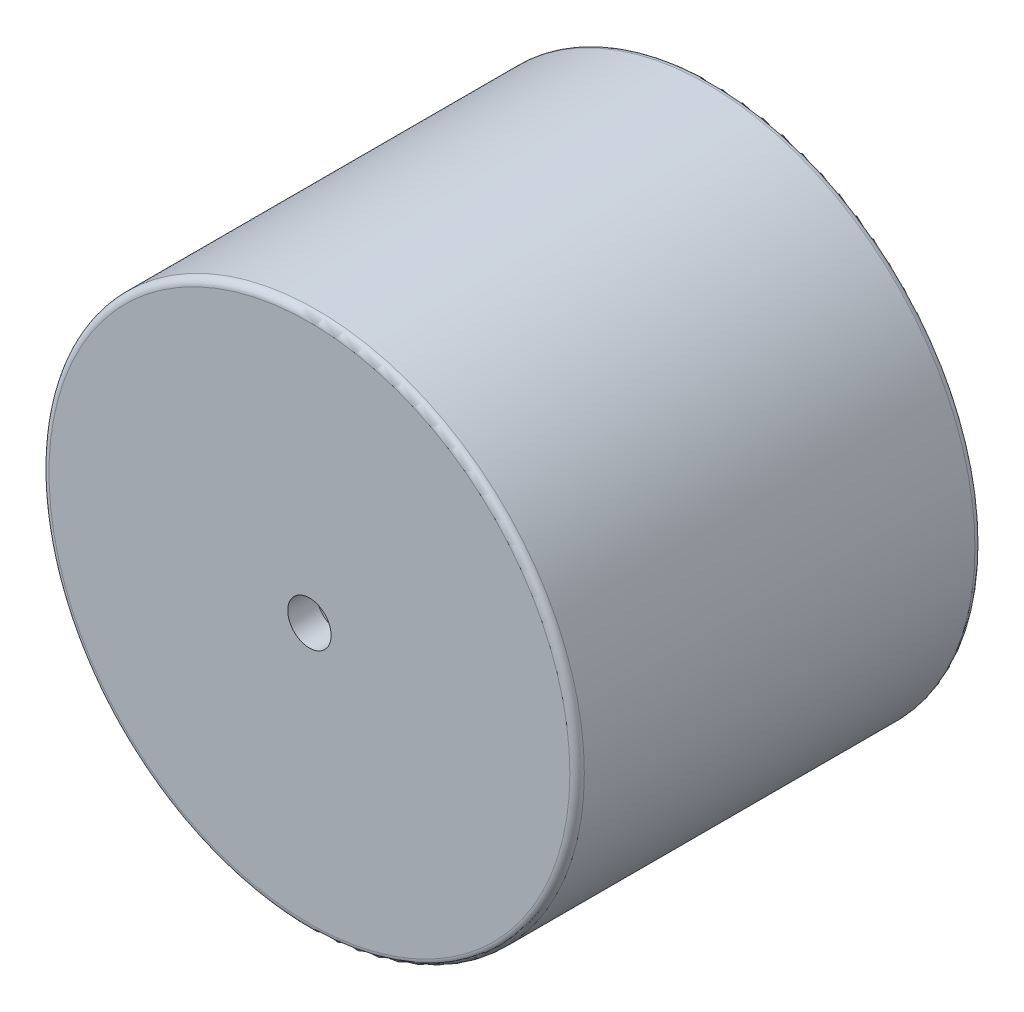
SolidWorks part; units mm, degrees
ref_plane "Front Plane" through (0, 0, 0) normal (0, 0, 1) x (1, 0, 0)
ref_plane "Top Plane" through (0, 0, 0) normal (0, 1, 0) x (1, 0, 0)
ref_plane "Right Plane" through (0, 0, 0) normal (1, 0, 0) x (0, 0, -1)
sketch "Sketch1" plane through (0, 0, 0) normal (0, 0, 1) x (1, 0, 0)
  circle A0 centre (0, 0) radius 18.5
  dimension "D1" = 37
extrude "Boss-Extrude1" add sketch "Sketch1" along normal blind 28
shell "Shell1" thickness 2 removed face at (18.5, 0, 28)
ref_plane "Plane1" through (0, 0, 26) normal (0, 0, 1) x (1, 0, 0)
sketch "Sketch2" plane through (0, 0, 26) normal (0, 0, 1) x (1, 0, 0)
  circle A0 centre (0, 0) radius 18.5
  dimension "D1" = 37
extrude "Boss-Extrude2" add sketch "Sketch2" along normal blind 2
sketch "Sketch3" plane through (0, 0, 0) normal (0, 0, -1) x (-1, 0, 0)
  circle A0 centre (0, 0) radius 13.5 construction
  circle A1 centre (5.3917, -7.8217) radius 4
  circle A2 centre (5.3917, -7.8217) radius 3
  dimension "D1" = 27
  dimension "D2" = 8
  dimension "D3" = 6
extrude "Boss-Extrude3" add sketch "Sketch3" along normal blind 10
sketch "Sketch4" plane through (0, 0, 0) normal (0, 0, -1) x (-1, 0, 0)
  circle A0 centre (5.3917, -7.8217) radius 3
  circle A2 centre (5.3917, -7.8217) radius 3 construction
extrude "Cut-Extrude1" cut sketch "Sketch4" against normal up to next
sketch "Sketch5" plane through (0, 0, 28) normal (0, 0, 1) x (1, 0, 0)
  circle A0 centre (0, 0) radius 1.5
  dimension "D1" = 3
extrude "Cut-Extrude2" cut sketch "Sketch5" against normal up to next
fillet "Fillet3" radius 0.5 3 edges at (18.5, 0, 28) (18.5, 0, 0) (-9.3917, -7.8217, -10)
sketch "Sketch7" plane through (0, 0, 0) normal (0, 0, -1) x (-1, 0, 0)
  line L0 (-23.6476, 0) -> (24.2128, 0) construction
  circle A0 centre (0, 0) radius 15 construction
  circle A1 centre (-15, 0) radius 1
  circle A2 centre (-7.5, 12.9904) radius 1
  circle A3 centre (7.5, 12.9904) radius 1
  circle A4 centre (15, 0) radius 1
  circle A5 centre (7.5, -12.9904) radius 1
  circle A6 centre (-7.5, -12.9904) radius 1
  point P19 (0, 0)
  dimension "D1" = 30
  dimension "D2" = 2
  dimension "D3" = 6
extrude "Cut-Extrude3" cut sketch "Sketch7" against normal up to next
sketch "Sketch8" plane through (0, 0, 0) normal (0, 0, -1) x (-1, 0, 0)
  arc A0 (9.288, -4.6883) -> (1.077, -10.3483) centre (0, 0) ccw
  arc A3 (9.288, -4.6883) -> (1.077, -10.3483) centre (5.3917, -7.8217) ccw
  dimension "D1" = 10
extrude "Cut-Extrude4" cut sketch "Sketch8" against normal blind 0.5
fillet "Fillet5" radius 0.25 1 edges at (5.9048, 8.5662, 0)
fillet "Fillet6" radius 0.25 1 edges at (-2.554, -3.705, 0)
sketch "Sketch9" plane through (0, 0, 0) normal (0, 0, -1) x (-1, 0, 0)
  line L0 (-25.4638, 0) -> (25.4638, 0) construction
  line L1 (21.0731, 12.1666) -> (-20.8289, -12.0256) construction
  circle A0 centre (0, 0) radius 15 construction
  circle A1 centre (-12.9904, -7.5) radius 1.5
  circle A2 centre (12.9904, 7.5) radius 1.5
  dimension "D2" = 30
  dimension "D3" = 3
  dimension "D4" = 3
  dimension "D1" = 30
extrude "Cut-Extrude5" cut sketch "Sketch9" against normal up to next
